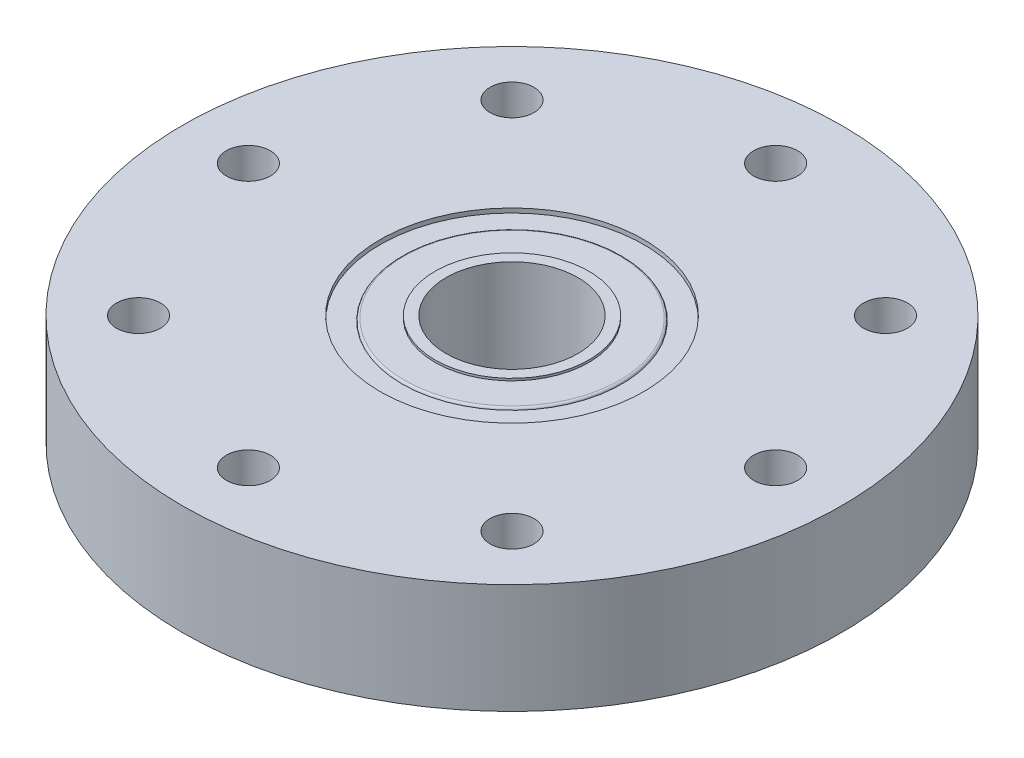
SolidWorks part; units mm, degrees
ref_plane "Front Plane" through (0, 0, 0) normal (0, 0, 1) x (1, 0, 0)
ref_plane "Top Plane" through (0, 0, 0) normal (0, 1, 0) x (1, 0, 0)
ref_plane "Right Plane" through (0, 0, 0) normal (1, 0, 0) x (0, 0, -1)
sketch "Sketch1" plane through (0, 0, 0) normal (0, 1, 0) x (1, 0, 0)
  line L0 (0, 12) -> (0, -12) construction
  line L1 (-12, 0) -> (12, 0) construction
  line L6 (8.5, 8.5) -> (-8.5, 8.5) construction
  circle A0 centre (0, 0) radius 15
  circle A2 centre (0, 12) radius 1
  circle A3 centre (0, -12) radius 1
  circle A4 centre (0, 0) radius 3
  circle A5 centre (-12, 0) radius 1
  circle A6 centre (12, 0) radius 1
  circle A7 centre (8.5, 8.5) radius 1
  circle A8 centre (8.5, -8.5) radius 1
  circle A9 centre (-8.5, -8.5) radius 1
  circle A10 centre (-8.5, 8.5) radius 1
  point P6 (0, 0)
  point P12 (0, 0)
  point P20 (0, 8.5)
  dimension "D1" = 4
extrude "Boss-Extrude1" add sketch "Sketch1" along normal blind 5
sketch "Sketch4" plane through (0, 5, 0) normal (0, 1, 0) x (1, 0, 0)
  line L0 (0, 5) -> (0, 6) construction
  line L1 (0, -3) -> (0, -3.5) construction
  circle A0 centre (0, 0) radius 5
  circle A1 centre (0, 0) radius 6
  circle A2 centre (0, 0) radius 3.5
  circle A3 centre (0, 0) radius 3 construction
extrude "Cut-Extrude1" cut sketch "Sketch4" against normal blind 0.2 contours A1 A0 region at (-5.8303, 5, 0)
extrude "Cut-Extrude2" cut sketch "Sketch4<3>" against normal blind 0.1 contours A0 A2 region at (-4.8586, 5, 0)
sketch "Sketch4<3>" plane through (0, 5, 0) normal (0, 1, 0) x (1, 0, 0) same geometry as "Sketch4"
fillet "Fillet1" radius 0.1 1 edges at (0, 4.9, 5)
